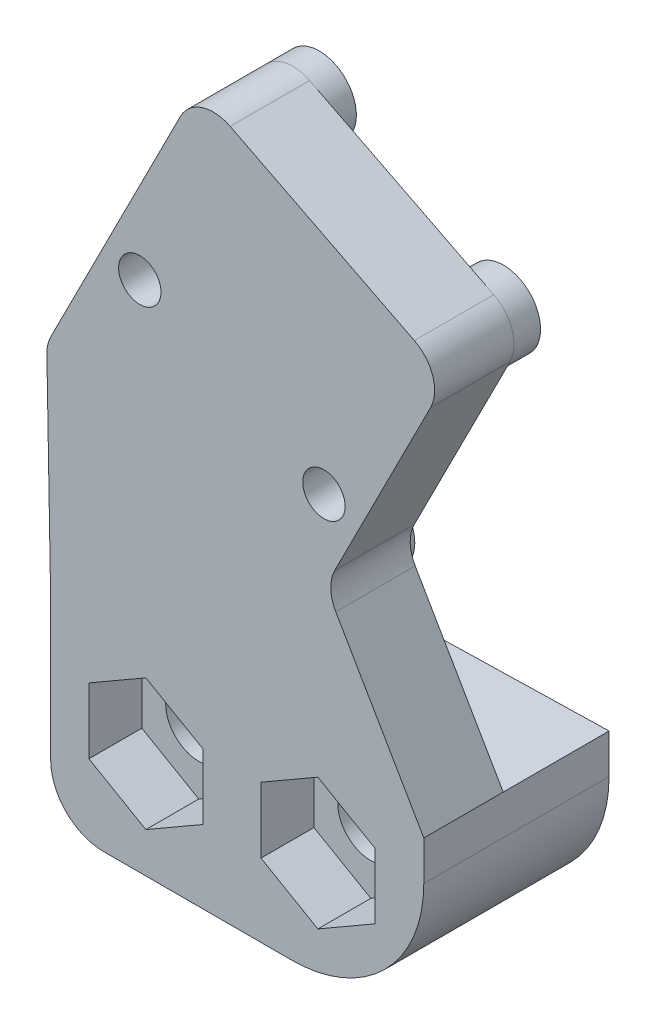
SolidWorks part; units mm, degrees
ref_plane "Front Plane" through (0, 0, 0) normal (0, 0, 1) x (1, 0, 0)
ref_plane "Top Plane" through (0, 0, 0) normal (0, 1, 0) x (1, 0, 0)
ref_plane "Right Plane" through (0, 0, 0) normal (1, 0, 0) x (0, 0, -1)
sketch "草图1" plane through (0, 0, 0) normal (0, 0, 1) x (1, 0, 0)
  line L0 (-26.9568, 10.4674) -> (-12.862, 10.4674)
  line L10 (-12.862, 10.4674) -> (-12.862, 16.9609)
  line L15 (-13.8519, 31.8057) -> (-20.8083, 35.334) construction
  line L16 (-20.8083, 35.334) -> (-25.5579, 25.9696) construction
  line L17 (-25.5579, 25.9696) -> (-18.6015, 22.4413) construction
  line L18 (-18.6015, 22.4413) -> (-13.8519, 31.8057) construction
  line L19 (-13.8519, 31.8057) -> (-25.5579, 25.9696) construction
  line L20 (-18.6015, 22.4413) -> (-20.8083, 35.334) construction
  line L21 (-16.862, 14.4674) -> (-23.362, 14.4674) construction
  line L24 (-16.6338, 26.3209) -> (-23.5902, 29.8491) construction
  line L25 (-22.0797, 24.2055) -> (-17.3301, 33.5698) construction
  line L26 (-27.1054, 26.0135) -> (-21.4236, 37.2158)
  line L27 (-21.4236, 37.2158) -> (-11.9701, 32.421)
  line L28 (-11.9701, 32.421) -> (-16.5684, 23.3548)
  line L29 (-16.5684, 23.3548) -> (-12.862, 16.9609)
  line L30 (-26.9568, 10.4674) -> (-26.9568, 17.6737)
  line L31 (-26.9568, 17.6737) -> (-27.1054, 26.0135)
  circle A17 centre (-16.862, 14.4674) radius 1.25
  circle A18 centre (-23.362, 14.4674) radius 1.25
  circle A20 centre (-13.8519, 31.8057) radius 1.4
  circle A21 centre (-20.8083, 35.334) radius 1.4
  circle A22 centre (-25.5579, 25.9696) radius 1.4
  circle A23 centre (-20.112, 28.085) radius 14 construction
  circle A26 centre (-18.6015, 22.4413) radius 1.4
  circle A27 centre (-16.6338, 26.3209) radius 0.8
  circle A28 centre (-23.5902, 29.8491) radius 0.8
  point P1 (-19.6111, 28.2351)
  point P11 (-20.112, 28.085)
  point P12 (-19.7049, 28.8877)
  point P24 (0, 0)
  point P26 (-19.7049, 28.8877)
  point P31 (-24.5684, 20.2178)
  point P32 (-27.1054, 25.9696)
  dimension "D5" = 2.5
  dimension "D6" = 2.5
  dimension "D4" = 4
  dimension "D8" = 1.6
  dimension "D9" = 2.8
  dimension "D2" = 1.6
  dimension "D10" = 2.8
  dimension "D3" = 2.8
  dimension "D7" = 2.8
  dimension "D13" = 28
  dimension "D15" = 7.8
  dimension "D12" = 10.5
  dimension "D11" = 4
  dimension "D14" = 6.5
  dimension "D16" = 0.9
extrude "凸台-拉伸1" add sketch "草图1" along normal blind 3 contours A17 | A18 | A27 | A28 | L10 L29 L28 L27 L26 L31 L30 L0
extrude "凸台-拉伸2" add sketch "草图1<3>" against normal blind 1 contours A20 | A21 | A22 | A26
sketch "草图1<3>" plane through (0, 0, 0) normal (0, 0, 1) x (1, 0, 0) same geometry as "草图1"
sketch "草图2" plane through (0, 0, 0) normal (0, 0, -1) x (-1, 0, 0)
  line L0 (12.862, 10.4674) -> (12.862, 16.9609) construction
  line L2 (12.862, 16.9609) -> (12.862, 10.4674)
  line L8 (23.7621, 16.5482) -> (19.1649, 16.8137)
  line L9 (19.1649, 16.8137) -> (12.862, 16.9609)
  line L15 (26.9568, 10.4674) -> (12.862, 10.4674) construction
  line L16 (12.862, 10.4674) -> (12.862, 16.9609) construction
  line L17 (12.862, 10.4674) -> (26.9568, 10.4674)
  line L18 (26.9568, 10.4674) -> (26.9568, 16.5482)
  line L19 (26.9568, 10.4674) -> (26.9568, 17.6737) construction
  line L20 (26.9568, 16.5482) -> (23.7621, 16.5482)
  circle A0 centre (16.862, 14.4674) radius 1.25
  circle A1 centre (23.362, 14.4674) radius 1.25
  point P1 (12.862, 16.9609)
  point P4 (19.6111, 13.64)
extrude "凸台-拉伸4" add sketch "草图2" along normal blind 4
sketch "草图3" plane through (0, 0, 3) normal (0, 0, 1) x (1, 0, 0)
  line L0 (-23.362, 16.9501) -> (-21.212, 15.7088)
  line L1 (-21.212, 15.7088) -> (-21.212, 13.2261)
  line L2 (-21.212, 13.2261) -> (-23.362, 11.9848)
  line L3 (-23.362, 11.9848) -> (-25.512, 13.2261)
  line L4 (-25.512, 13.2261) -> (-25.512, 15.7088)
  line L5 (-25.512, 15.7088) -> (-23.362, 16.9501)
  line L6 (-23.362, 16.9501) -> (-23.362, 11.9848) construction
  line L7 (-25.512, 15.7088) -> (-21.212, 13.2261) construction
  line L8 (-16.862, 16.9501) -> (-14.712, 15.7088)
  line L9 (-14.712, 15.7088) -> (-14.712, 13.2261)
  line L10 (-14.712, 13.2261) -> (-16.862, 11.9848)
  line L11 (-16.862, 11.9848) -> (-19.012, 13.2261)
  line L12 (-19.012, 13.2261) -> (-19.012, 15.7088)
  line L13 (-19.012, 15.7088) -> (-16.862, 16.9501)
  line L14 (-16.862, 16.9501) -> (-16.862, 11.9848) construction
  line L15 (-19.012, 15.7088) -> (-14.712, 13.2261) construction
  point P2 (-16.862, 14.4674)
  point P7 (-23.362, 14.4674)
  point P17 (-16.862, 14.4674)
  dimension "D1" = 120
  dimension "D2" = 240
  dimension "D3" = 4.3
  dimension "D4" = 120
  dimension "D5" = 240
  dimension "D6" = 4.3
extrude "切除-拉伸1" cut sketch "草图3" against normal blind 2
fillet "圆角5" radius 1.4 4 edges at (-27.1054, 26.0135, 1.5) (-16.5684, 23.3548, 1.5) (-11.9701, 32.421, 1.5) (-21.4236, 37.2158, 1.5)
fillet "圆角6" radius 5 1 edges at (-12.862, 10.4674, -0.5)
fillet "圆角7" radius 2 1 edges at (-26.9568, 10.4674, -0.5)
